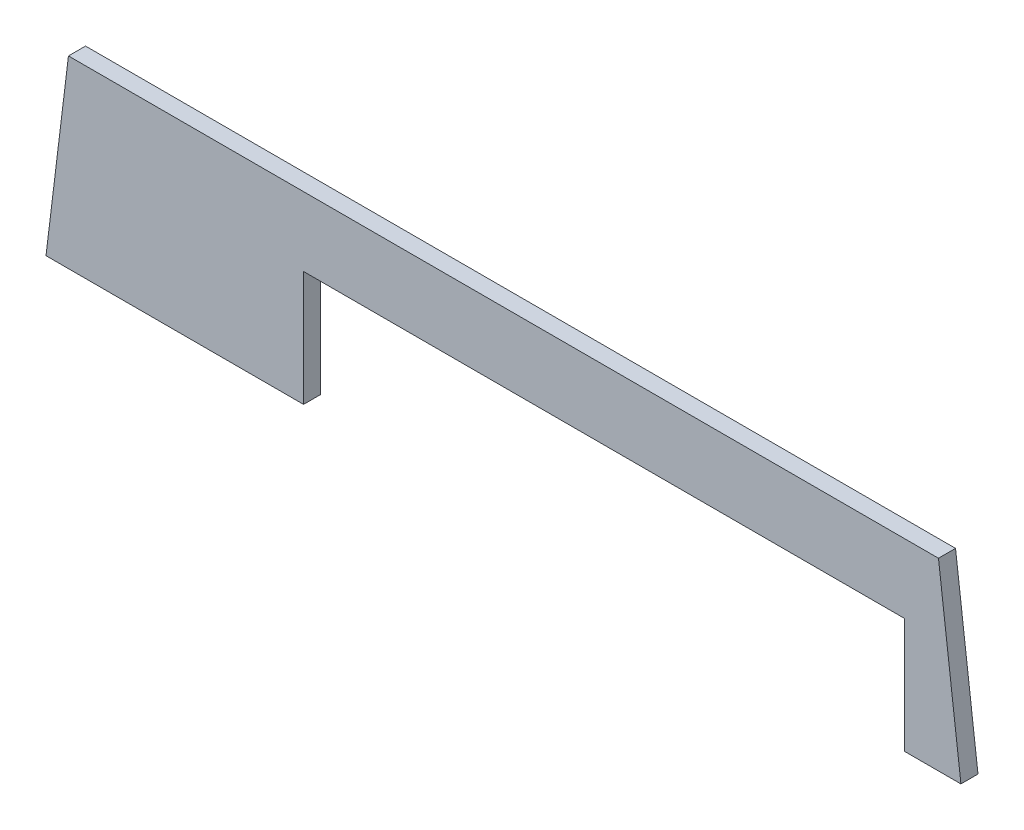
SolidWorks part; units mm, degrees
ref_plane "Front Plane" through (0, 0, 0) normal (0, 0, 1) x (1, 0, 0)
ref_plane "Top Plane" through (0, 0, 0) normal (0, 1, 0) x (1, 0, 0)
ref_plane "Right Plane" through (0, 0, 0) normal (1, 0, 0) x (0, 0, -1)
ref_axis "Axis1" through (0, -55, 0) along (0, 1, 0)
sketch "Model" plane through (0, 0, 0) normal (0, 0, 1) x (1, 0, 0)
  line L0 (558.1838, 135.8593) -> (48.9139, 135.8593)
  line L1 (48.9139, 135.8593) -> (35.7697, 28.0043)
  line L2 (35.7697, 28.0043) -> (186.5288, 28.0043)
  line L3 (186.5288, 28.0043) -> (186.5288, 95.3969)
  line L4 (186.5288, 95.3969) -> (538.3162, 95.3969)
  line L5 (538.3162, 95.3969) -> (538.3162, 28.0043)
  line L6 (538.3162, 28.0043) -> (571.328, 28.0043)
  line L7 (571.328, 28.0043) -> (558.1838, 135.8593)
extrude "Boss-Extrude1" add sketch "Model" along normal blind 10
